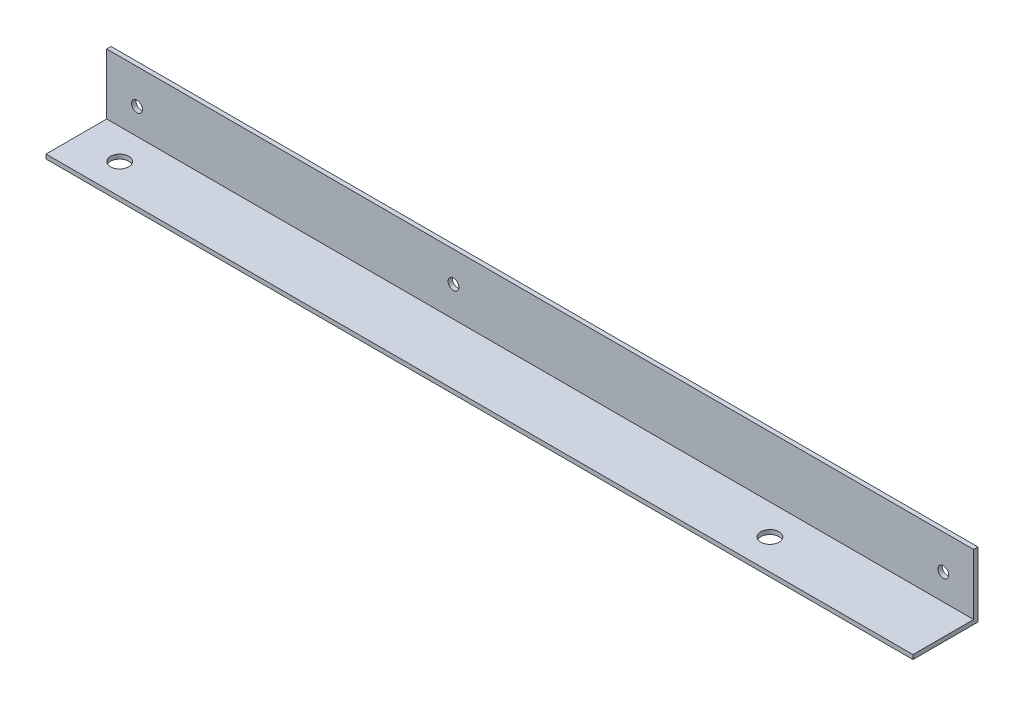
SolidWorks part; units mm, degrees
ref_plane "正面" through (0, 0, 0) normal (0, 0, 1) x (1, 0, 0)
ref_plane "平面" through (0, 0, 0) normal (0, 1, 0) x (1, 0, 0)
ref_plane "右側面" through (0, 0, 0) normal (1, 0, 0) x (0, 0, -1)
sketch "ｽｹｯﾁ1" plane through (0, 0, 0) normal (0, 0, 1) x (1, 0, 0)
  line L1 (0, 0) -> (200, 0)
  line L2 (0, 0) -> (0, 15)
  line L3 (0, 15) -> (200, 15)
  line L4 (200, 0) -> (200, 15)
  dimension "D1" = 200
  dimension "D2" = 15
extrude "ﾎﾞｽ - 押し出し1" add sketch "ｽｹｯﾁ1" along normal blind 1
sketch "ｽｹｯﾁ2" plane through (0, 0, 1) normal (0, 0, 1) x (1, 0, 0)
  line L1 (0, 0) -> (200, 0)
  line L2 (0, 0) -> (0, 1)
  line L3 (0, 1) -> (200, 1)
  line L4 (200, 0) -> (200, 1)
  dimension "D1" = 200
  dimension "D2" = 1
extrude "ﾎﾞｽ - 押し出し2" add sketch "ｽｹｯﾁ2" along normal blind 14
hole_wizard "M5x0.8 ねじ穴1" positions "ｽｹｯﾁ3" profile "ｽｹｯﾁ4" tap size "M5x0.8" standard "JIS" end condition through all
sketch "ｽｹｯﾁ3" plane through (0, 0, 0) normal (0, -1, 0) x (-1, 0, 0)
  line L0 (0, -15) -> (0, 0) construction
  line L1 (0, -15) -> (-200, -15) construction
  point P0 (-10, -8)
  point P2 (-160, -8)
  dimension "D1" = 10
  dimension "D2" = 7
  dimension "D3" = 150
  dimension "D4" = 7
sketch "ｽｹｯﾁ4" plane through (10, 0, 8) normal (1, 0, 0) x (0, 0, -1)
  line L0 (0, 0) -> (0, 15)
  line L1 (0, 15) -> (2.1, 15)
  line L2 (2.1, 15) -> (2.1, 0)
  line L5 (2.1, 0) -> (0, 0)
  line L11 (0, -6.35) -> (0, 107.95) construction
  dimension "次ｻｰﾌｪｽまでのねじ下穴ﾄﾞﾘﾙ直径" = 4.2
  dimension "次ｻｰﾌｪｽまでのねじ下穴ﾄﾞﾘﾙの深さ" = 15
cosmetic thread "穴のねじ山1" parameters "D2"=5
cosmetic thread "穴のねじ山2" parameters "D2"=5
hole_wizard "M3x0.5 ねじ穴1" positions "ｽｹｯﾁ5" profile "ｽｹｯﾁ6" tap size "M3x0.5" standard "JIS" end condition through all
sketch "ｽｹｯﾁ5" plane through (0, 0, 0) normal (0, 0, -1) x (-1, 0, 0)
  line L0 (-200, 0) -> (-200, 15) construction
  line L1 (0, 0) -> (-200, 0) construction
  point P0 (-193, 7)
  dimension "D1" = 7
  dimension "D2" = 7
sketch "ｽｹｯﾁ6" plane through (193, 7, 0) normal (1, 0, 0) x (0, 1, 0)
  line L0 (0, 0) -> (0, 15)
  line L1 (0, 15) -> (1.25, 15)
  line L2 (1.25, 15) -> (1.25, 0)
  line L5 (1.25, 0) -> (0, 0)
  line L11 (0, -6.35) -> (0, 107.95) construction
  dimension "次ｻｰﾌｪｽまでのねじ下穴ﾄﾞﾘﾙ直径" = 2.5
  dimension "次ｻｰﾌｪｽまでのねじ下穴ﾄﾞﾘﾙの深さ" = 15
cosmetic thread "穴のねじ山3" parameters "D2"=3
hole_wizard "M3x0.5 ねじ穴2" positions "ｽｹｯﾁ7" profile "ｽｹｯﾁ8" tap size "M3x0.5" standard "JIS" end condition through all
sketch "ｽｹｯﾁ7" plane through (0, 0, 1) normal (0, 0, 1) x (1, 0, 0)
  line L0 (200, 15) -> (0, 15) construction
  line L1 (200, 1) -> (200, 15) construction
  point P0 (80, 8)
  point P7 (200, 8)
  dimension "D1" = 7
  dimension "D2" = 120
sketch "ｽｹｯﾁ8" plane through (80, 8, 1) normal (1, 0, 0) x (0, -1, 0)
  line L0 (0, 0) -> (0, 1)
  line L1 (0, 1) -> (1.25, 1)
  line L2 (1.25, 1) -> (1.25, 0)
  line L5 (1.25, 0) -> (0, 0)
  line L11 (0, -6.35) -> (0, 107.95) construction
  dimension "次ｻｰﾌｪｽまでのねじ下穴ﾄﾞﾘﾙ直径" = 2.5
  dimension "次ｻｰﾌｪｽまでのねじ下穴ﾄﾞﾘﾙの深さ" = 1
cosmetic thread "穴のねじ山4" parameters "D2"=3
ref_plane "平面1" through (100, 0, 0) normal (1, 0, 0) x (0, 0, -1)
mirror "ﾐﾗｰ1" about plane through (100, 0, 0) normal (1, 0, 0) of "M3x0.5 ねじ穴1"
